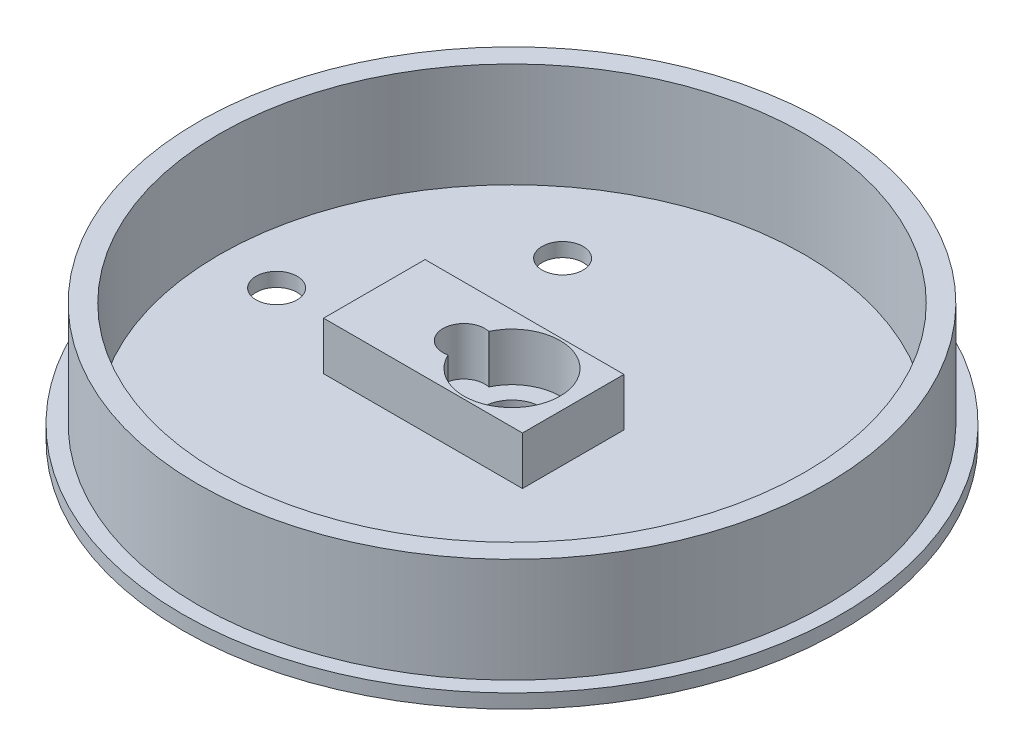
SolidWorks part; units mm, degrees
ref_plane "Front Plane" through (0, 0, 0) normal (0, 0, 1) x (1, 0, 0)
ref_plane "Top Plane" through (0, 0, 0) normal (0, 1, 0) x (1, 0, 0)
ref_plane "Right Plane" through (0, 0, 0) normal (1, 0, 0) x (0, 0, -1)
sketch "Sketch1" plane through (0, 0, 0) normal (0, 1, 0) x (1, 0, 0)
  line L0 (-28.575, 0) -> (28.575, 0) construction
  line L1 (0, 0) -> (0, 7.4083) construction
  line L2 (-28.575, 0) -> (28.575, 0) construction
  line L8 (5.842, 0) -> (-16.7132, 0)
  line L9 (-28.575, 2.4892) -> (28.575, 2.4892)
  line L10 (-28.575, -2.4892) -> (28.575, -2.4892)
  line L11 (5.842, 0) -> (5.842, 6.1595)
  line L12 (5.842, 6.1595) -> (-16.7132, 6.1595)
  line L13 (-16.7132, 0) -> (-16.7132, 6.1595)
  line L14 (5.842, 0) -> (-16.7132, 0)
  line L15 (5.842, 0) -> (5.842, -6.1595)
  line L16 (5.842, -6.1595) -> (-16.7132, -6.1595)
  line L17 (-16.7132, 0) -> (-16.7132, -6.1595)
  line L18 (7.4295, 6.1595) -> (5.842, 6.1595)
  line L19 (7.4295, 6.1595) -> (7.4295, -6.1595)
  line L20 (7.4295, -6.1595) -> (5.842, -6.1595)
  line L21 (5.842, 6.1595) -> (5.842, -6.1595)
  circle A0 centre (-28.575, 0) radius 4.445
  circle A1 centre (-28.575, 0) radius 2.4892
  circle A2 centre (28.575, 0) radius 2.4892
  circle A3 centre (28.575, 0) radius 4.445
  arc A4 (-28.575, 2.4892) -> (-28.575, -2.4892) centre (-28.575, 0) ccw
  arc A5 (28.575, -2.4892) -> (28.575, 2.4892) centre (28.575, 0) ccw
  circle A6 centre (0, 0) radius 3.556
  circle A7 centre (0, 0) radius 5.842
  circle A8 centre (-5.842, 0) radius 2.54
  point P4 (0, 0)
  point P15 (0, 0)
  dimension "D2" = 4.9784
  dimension "D3" = 8.89
  dimension "D4" = 2.4892
  dimension "D5" = 7.112
  dimension "D6" = 11.684
  dimension "D7" = 5.08
  dimension "D1" = 57.15
  dimension "D8" = 22.5552
  dimension "D9" = 12.319
  dimension "D10" = 1.5875
extrude "Boss-Extrude1" add sketch "Sketch1" along normal blind 1.7018 contours A1 L10 A0 L9 | A1 L9 A0 L10 | A0 L10 L17 L13 L9 | A8 L10 L17 L16 L15 A7 | A8 L8 L17 L10 | A8 L9 L13 L8 | A8 L9 A7 L11 L12 L13 | L19 L18 L11 L9 | L20 L19 L10 L15 | L19 L9 L11 L15 L10 | A7 L11 L9 | A7 L10 L15 | L10 A7 L8 A6 | L8 A7 L9 A6 | L9 A7 A6 | L10 A7 A6 | A8 A7 L10 A6 | A8 A6 L9 A7 | L10 A3 L9 L19 | A3 L10 A2 L9 | A3 L9 A2 L10 | A6 A8 A7 L8 | A7 A8 A6 L8 | L9 A8 | A7 A8 L9 L14 | L10 A8 | L10 A8 A7 L14 | A8 L10 A7 | A8 A7 L9 region at (4.4373, 0, 1.2813) region at (5.6764, 0, -1.873) region at (6.6358, 0, 0) region at (4.4373, 0, -1.2813) region at (5.6764, 0, 1.873) region at (6.6357, 0, -4.3243) region at (-7.8471, 0, -4.527) region at (-7.8471, 0, 4.527) region at (6.6358, 0, 4.3243) region at (0, 0, -4.0333) region at (0, 0, 4.0333) region at (15.9036, 0, 0) region at (-5.3037, 0, -2.4859) region at (-3.6624, 0, -2.0301) region at (-3.6624, 0, 2.0301) region at (-5.3037, 0, 2.4859) region at (-4.7114, 0, 1.0165) region at (-4.7114, 0, -1.0165) region at (29.8414, 0, -4.135) region at (25.5549, 0, 0) region at (-6.8205, 0, -1.1389) region at (-5.842, 0, -2.5095) region at (-5.842, 0, 2.5095) region at (-6.8205, 0, 1.1389) region at (-20.5472, 0, 0) region at (-12.2767, 0, -1.2839) region at (-12.2767, 0, 1.2839) region at (-25.5549, 0, 0) region at (-26.7337, 0, -2.6097)
extrude "Boss-Extrude2" add sketch "Sketch1<4>" along normal blind 5.842 from surface contours A8 L10 L17 L16 L15 A7 | A8 L9 L13 L8 | A8 L9 A7 L11 L12 L13 | L19 L18 L11 L9 | L19 L9 L11 L15 L10 | L20 L19 L10 L15 | A7 L10 L15 | A7 L11 L9 | A8 L8 L17 L10 region at (5.6764, 0, -1.873) region at (6.6358, 0, 0) region at (5.6764, 0, 1.873) region at (6.6357, 0, -4.3243) region at (-7.8471, 0, -4.527) region at (-7.8471, 0, 4.527) region at (6.6358, 0, 4.3243) region at (-12.2767, 0, -1.2839) region at (-12.2767, 0, 1.2839) starting at face at (28.575, 1.7018, 2.4892)
sketch "Sketch1<4>" plane through (0, 0, 0) normal (0, 1, 0) x (1, 0, 0) same geometry as "Sketch1"
sketch "Sketch3" plane through (0, 7.5438, 0) normal (0, 1, 0) x (1, 0, 0)
  line L0 (-14.348, 20.4911) -> (14.348, -20.4911) construction
  line L1 (-12.309, 21.9188) -> (16.387, -19.0633)
  line L2 (-16.387, 19.0633) -> (12.309, -21.9188)
  circle A0 centre (-14.348, 20.4911) radius 2.4892
  circle A1 centre (14.348, -20.4911) radius 2.4892
  circle A2 centre (-14.348, 20.4911) radius 4.445
  circle A3 centre (14.348, -20.4911) radius 4.445
  arc A4 (-12.309, 21.9188) -> (-16.387, 19.0633) centre (-14.348, 20.4911) ccw
  arc A5 (12.309, -21.9188) -> (16.387, -19.0633) centre (14.348, -20.4911) ccw
  point P8 (0, 0)
  line M8 (7.4295, 6.1595) -> (-16.7132, 6.1595)
  line M10 (-16.7132, -6.1595) -> (7.4295, -6.1595)
  dimension "D1" = 2.4892
  dimension "D2" = 4.9784
  dimension "D3" = 4.9784
  dimension "D4" = 8.89
  dimension "D5" = 8.89
extrude "Boss-Extrude3" add sketch "Sketch3" along normal blind 1.7018 from surface contours A0 L0 A2 L1 | L1 A2 L2 A0 | L0 A0 L2 A2 | L0 A2 L2 M8 | A2 L0 L1 M8 | L0 L2 A3 M10 | L0 A3 L1 M10 | L2 A3 L1 A1 | A3 L0 A1 L1 | L0 A3 L2 A1 region at (-11.5186, 7.5438, -18.7854) region at (-13.7129, 7.5438, -17.2489) region at (-6.8225, 7.5438, -11.9769) region at (-9.377, 7.5438, -11.2509) region at (-15.4339, 7.5438, -17.4829) region at (9.377, 7.5438, 11.2509) region at (6.8225, 7.5438, 11.9769) region at (13.7129, 7.5438, 17.2489) region at (11.5186, 7.5438, 18.7854) region at (17.3769, 7.5438, 17.4118) starting at face at (28.575, 0, 2.4892)
sketch "Sketch5" plane through (0, 0, 0) normal (0, -1, 0) x (1, 0, 0)
  circle A0 centre (0, 0) radius 40.005
  line M4 (7.4295, 2.4892) -> (7.4295, 6.1595)
  line M5 (7.4295, 6.1595) -> (7.3517, 6.1595)
  line M6 (7.3517, 6.1595) -> (14.2748, 16.0467)
  arc M7 (14.2748, 16.0467) -> (10.1967, 18.9022) centre (14.348, 20.4911) ccw
  line M8 (10.1967, 18.9022) -> (1.2742, 6.1595)
  line M9 (1.2742, 6.1595) -> (-16.7132, 6.1595)
  line M10 (-16.7132, 6.1595) -> (-16.7132, 2.4892)
  line M11 (-16.7132, 2.4892) -> (-24.8924, 2.4892)
  arc M12 (-24.8924, 2.4892) -> (-24.8924, -2.4892) centre (-28.575, 0) ccw
  line M13 (-24.8924, -2.4892) -> (-16.7132, -2.4892)
  line M14 (-16.7132, -2.4892) -> (-16.7132, -6.1595)
  line M15 (-16.7132, -6.1595) -> (-7.3517, -6.1595)
  line M16 (-7.3517, -6.1595) -> (-14.2748, -16.0467)
  arc M17 (-14.2748, -16.0467) -> (-10.1967, -18.9022) centre (-14.348, -20.4911) ccw
  line M18 (-10.1967, -18.9022) -> (-1.2742, -6.1595)
  line M19 (-1.2742, -6.1595) -> (7.4295, -6.1595)
  line M20 (7.4295, -6.1595) -> (7.4295, -2.4892)
  line M21 (7.4295, -2.4892) -> (24.8924, -2.4892)
  arc M22 (24.8924, -2.4892) -> (24.8924, 2.4892) centre (28.575, 0) ccw
  line M23 (24.8924, 2.4892) -> (7.4295, 2.4892)
  dimension "D1" = 80.01
extrude "Boss-Extrude5" add sketch "Sketch5" against normal up to surface (1.7018 mm away) contours A0 M4 M23 M22 M21 M20 M19 M18 M17 M16 M15 M14 M13 M12 M11 M10 M9 M8 M7 M6 M5 region at (-38.8735, 0, 0) up to face at (9.4398, 1.7018, 13.4814)
sketch "Sketch6" plane through (0, 1.7018, 0) normal (0, 1, 0) x (1, 0, 0)
  circle A0 centre (0, 0) radius 38.1
  circle A1 centre (0, 0) radius 35.56
  dimension "D1" = 76.2
  dimension "D2" = 71.12
extrude "Boss-Extrude6" add sketch "Sketch6" along normal blind 12.7 contours A0 A1 region at (-37.0224, 1.7018, 0)
